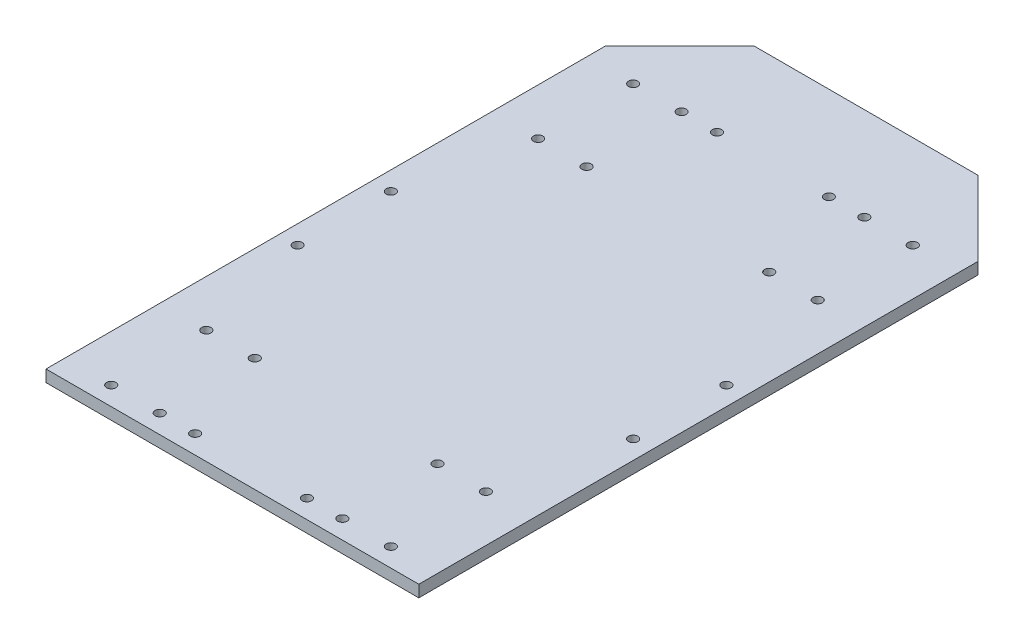
SolidWorks part; units mm, degrees
ref_plane "Front Plane" through (0, 0, 0) normal (0, 0, 1) x (1, 0, 0)
ref_plane "Top Plane" through (0, 0, 0) normal (0, 1, 0) x (1, 0, 0)
ref_plane "Right Plane" through (0, 0, 0) normal (1, 0, 0) x (0, 0, -1)
sketch "Sketch1" plane through (0, 0, 0) normal (0, 1, 0) x (1, 0, 0)
  line L0 (-200, 300) -> (-160, 340)
  line L1 (0, 0) -> (-200, 0)
  line L2 (0, 0) -> (0, 300)
  line L3 (0, 300) -> (-200, 300)
  line L4 (-200, 0) -> (-200, 300)
  line L5 (-160, 340) -> (-40, 340)
  line L6 (-40, 340) -> (0, 300)
  line L7 (-175, 290) -> (-149, 290) construction
  line L8 (-175, 239) -> (-149, 239) construction
  line L9 (-175, 290) -> (-175, 239) construction
  line L10 (-175, 290) -> (-200, 290) construction
  line L11 (-100, 300) -> (-100, 0) construction
  line L12 (-200, 150) -> (0, 150) construction
  circle A0 centre (-175, 290) radius 2.5
  circle A1 centre (-149, 290) radius 2.5
  circle A2 centre (-175, 239) radius 2.5
  circle A3 centre (-149, 239) radius 2.5
  circle A4 centre (-51, 290) radius 2.5
  circle A5 centre (-25, 290) radius 2.5
  circle A6 centre (-25, 239) radius 2.5
  circle A7 centre (-51, 239) radius 2.5
  circle A8 centre (-25, 10) radius 2.5
  circle A9 centre (-25, 61) radius 2.5
  circle A10 centre (-51, 61) radius 2.5
  circle A11 centre (-51, 10) radius 2.5
  circle A12 centre (-149, 10) radius 2.5
  circle A13 centre (-149, 61) radius 2.5
  circle A14 centre (-175, 10) radius 2.5
  circle A15 centre (-175, 61) radius 2.5
  dimension "D9" = 5
  dimension "D1" = 45
  dimension "D2" = 40
  dimension "D3" = 300
  dimension "D4" = 200
  dimension "D5" = 51
  dimension "D6" = 26
  dimension "D7" = 25
  dimension "D8" = 10
extrude "Boss-Extrude1" add sketch "Sketch1" along normal blind 6.35 contours L4 L1 L2 L3 | L6 L5 L0 L3 region at (-100, 0, -318.3333) region at (-100, 0, -150)
sketch "Sketch2" plane through (0, 6.35, 0) normal (0, 1, 0) x (1, 0, 0)
  line L0 (-100, 0) -> (-100, 50000) construction
  line L1 (0, 0) -> (-200, 0) construction
  line L2 (-160, 340) -> (-40, 340) construction
  line L3 (-145, 150) -> (49855, 150) construction
  line L4 (-200, 0) -> (-200, 300) construction
  line L5 (0, 0) -> (0, 300) construction
  circle A0 centre (-70, 10) radius 2.5
  circle A2 centre (-10, 125) radius 2.5
  circle A3 centre (-190, 125) radius 2.5
  circle A4 centre (-130, 10) radius 2.5
  circle A5 centre (-70, 290) radius 2.5
  circle A6 centre (-10, 175) radius 2.5
  circle A7 centre (-190, 175) radius 2.5
  circle A8 centre (-130, 290) radius 2.5
  point P4 (-100, 0)
  point P7 (-100, 340)
  point P12 (-200, 150)
  point P15 (0, 150)
  dimension "D1" = 5
  dimension "D2" = 10
  dimension "D3" = 30
  dimension "D4" = 10
  dimension "D5" = 25
extrude "Cut-Extrude1" cut sketch "Sketch2" against normal blind 10
